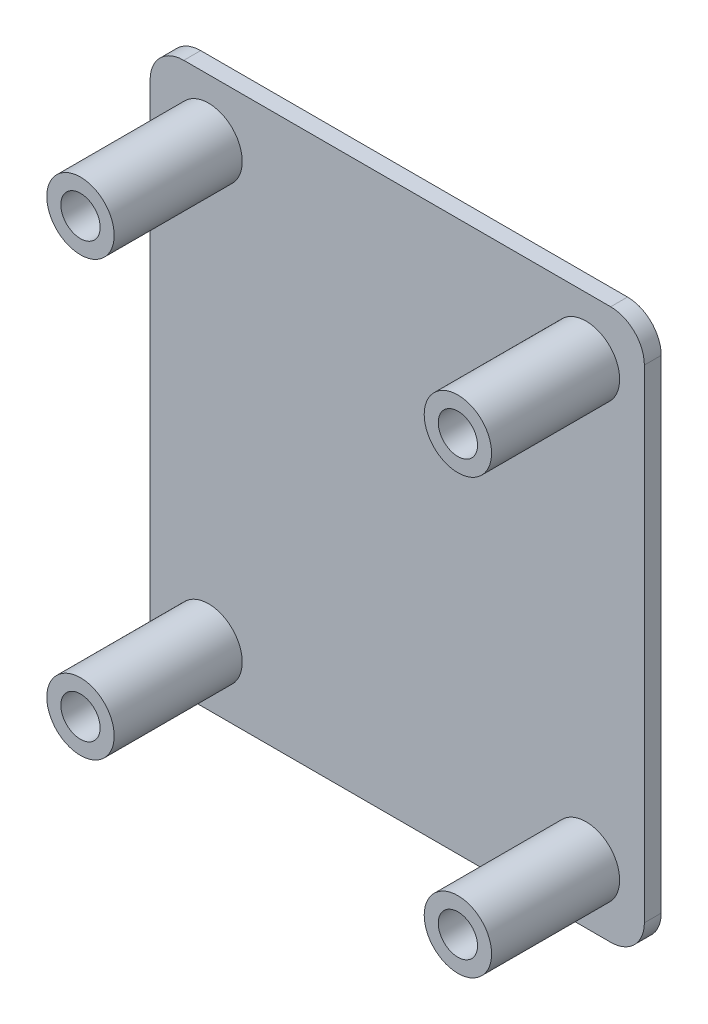
SolidWorks part; units mm, degrees
ref_plane "前视基准面" through (0, 0, 0) normal (0, 0, 1) x (1, 0, 0)
ref_plane "上视基准面" through (0, 0, 0) normal (0, 1, 0) x (1, 0, 0)
ref_plane "右视基准面" through (0, 0, 0) normal (1, 0, 0) x (0, 0, -1)
other "Configuration Table"
sketch "草图1" plane through (0, 0, 0) normal (0, 0, 1) x (1, 0, 0)
  line L1 (3, 0) -> (41, 0)
  line L2 (0, 3) -> (0, 46)
  line L3 (3, 49) -> (41, 49)
  line L4 (44, 3) -> (44, 46)
  arc A0 (3, 0) -> (0, 3) centre (3, 3) cw
  arc A1 (41, 0) -> (44, 3) centre (41, 3) ccw
  arc A2 (41, 49) -> (44, 46) centre (41, 46) cw
  arc A3 (0, 46) -> (3, 49) centre (3, 46) cw
  point P5 (0, 0)
  point P8 (0, 0)
  point P11 (44, 0)
  point P14 (44, 49)
  point P17 (0, 49)
  dimension "D3" = 3
  dimension "D1" = 44
  dimension "D2" = 49
extrude "凸台-拉伸1" add sketch "草图1" along normal blind 1.5
sketch "草图5" plane through (0, 0, 1.5) normal (0, 0, 1) x (1, 0, 0)
  line L0 (41, 49) -> (3, 49) construction
  line L1 (0, 46) -> (0, 3) construction
  line L2 (22, 49) -> (22, -1.9827) construction
  line L3 (0, 24.5) -> (49.356, 24.5) construction
  circle A0 centre (5.2, 43.8) radius 1.75
  circle A1 centre (38.8, 43.8) radius 1.75
  circle A2 centre (38.8, 5.2) radius 1.75
  circle A3 centre (5.2, 5.2) radius 1.75
  point P10 (0, 0)
  dimension "D1" = 3.5
  dimension "D2" = 5.2
  dimension "D3" = 5.2
extrude "切除-拉伸2" cut sketch "草图5" against normal up to surface (1.5 mm away) up to face at (22, 24.5, 0)
sketch "草图6" plane through (0, 0, 1.5) normal (0, 0, 1) x (1, 0, 0)
  line L0 (22, 49) -> (22, -3.6199) construction
  line L1 (41, 49) -> (3, 49) construction
  line L2 (0, 24.5) -> (52.2573, 24.5) construction
  line L3 (0, 46) -> (0, 3) construction
  circle A0 centre (5.2, 43.8) radius 1.75
  circle A1 centre (5.2, 43.8) radius 3
  circle A2 centre (38.8, 43.8) radius 1.75
  circle A3 centre (38.8, 43.8) radius 3
  circle A4 centre (38.8, 5.2) radius 1.75
  circle A5 centre (38.8, 5.2) radius 3
  circle A6 centre (5.2, 5.2) radius 1.75
  circle A7 centre (5.2, 5.2) radius 3
  dimension "D1" = 3.5
  dimension "D2" = 6
extrude "凸台-拉伸2" add sketch "草图6" along normal blind 11.4
